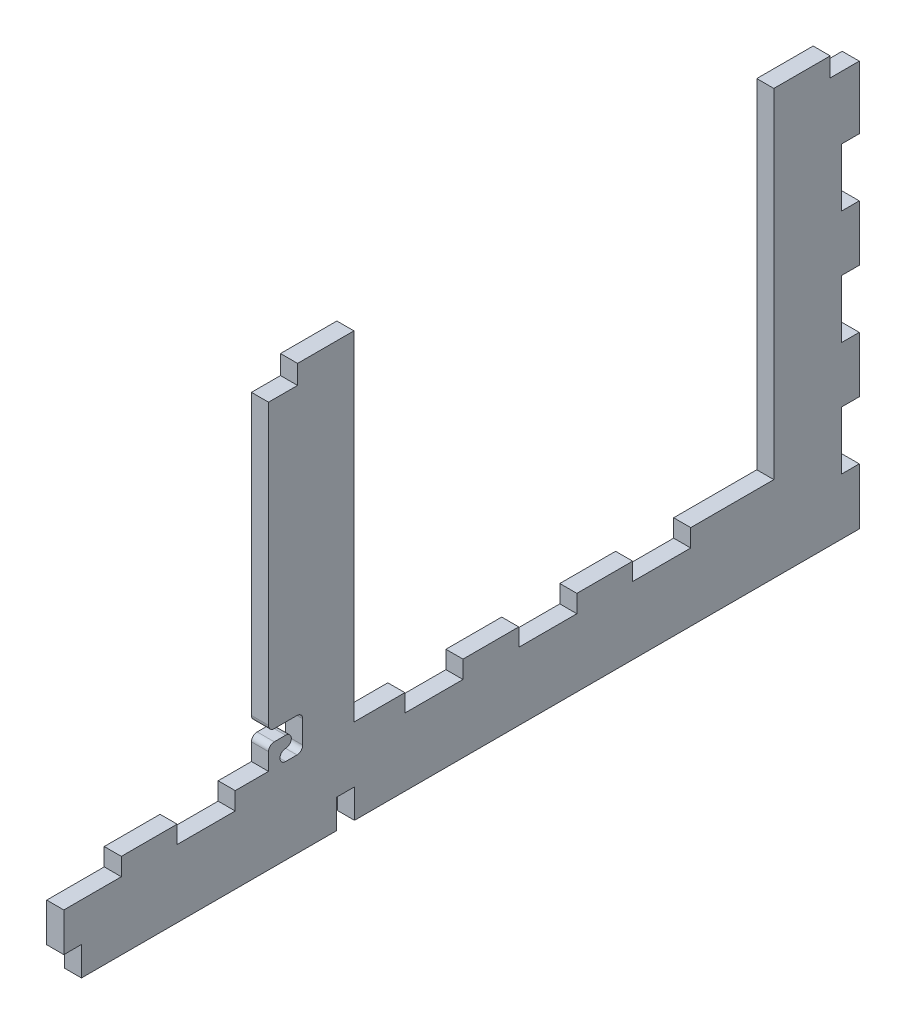
SolidWorks part; units mm, degrees
ref_plane "Front Plane" through (0, 0, 0) normal (0, 0, 1) x (1, 0, 0)
ref_plane "Top Plane" through (0, 0, 0) normal (0, 1, 0) x (1, 0, 0)
ref_plane "Right Plane" through (0, 0, 0) normal (1, 0, 0) x (0, 0, -1)
sketch "Sketch1" plane through (0, 0, 0) normal (0, 1, 0) x (1, 0, 0)
  line L0 (0, 0) -> (0, 103.7444) construction
  line L1 (-36.8722, 0) -> (36.8722, 0) construction
  line L2 (-36.8722, 0) -> (-36.8722, 103.7444)
  line L3 (-36.8722, 103.7444) -> (36.8722, 103.7444)
  line L4 (36.8722, 0) -> (36.8722, 103.7444)
  line L5 (36.8722, 103.7444) -> (36.8722, 0) construction
  line L6 (45.8722, 103.7444) -> (-45.8722, 103.7444) construction
  line L7 (21.0585, 67.686) -> (21.0585, 0)
  line L8 (-21.0585, 67.686) -> (-21.0585, 0)
  line L9 (-36.8722, 0) -> (-21.0585, 0)
  line L10 (21.0585, 0) -> (36.8722, 0)
  line L11 (31.8722, 103.7444) -> (31.8722, 88.7444) construction
  line L12 (34.8722, 103.7444) -> (34.8722, 88.7444) construction
  line L13 (31.8722, 93.7444) -> (34.8722, 93.7444) construction
  line L14 (31.8722, 10) -> (34.8722, 10) construction
  line L15 (31.8722, 88.7444) -> (34.8722, 88.7444) construction
  line L16 (31.8722, 15) -> (34.8722, 15) construction
  line L17 (31.8722, 15) -> (31.8722, 0) construction
  line L18 (34.8722, 15) -> (34.8722, 0) construction
  line L19 (33.3722, 93.7444) -> (33.3722, 88.7444) construction
  line L20 (33.3722, 15) -> (33.3722, 10) construction
  line L21 (34.8722, 100.7444) -> (-34.8722, 100.7444) construction
  line L22 (-34.8722, 100.7444) -> (-34.8722, 103.7444) construction
  line L23 (56.7, -65.95) -> (59.7, -65.95) construction
  arc A0 (21.0585, 67.686) -> (-21.0585, 67.686) centre (0, 67.686) ccw construction
  arc A1 (21.0585, 67.686) -> (-21.0585, 67.686) centre (0, 67.686) ccw
  circle A2 centre (26.5585, 78.4307) radius 1.6 construction
  circle A3 centre (-26.5585, 78.4307) radius 1.6 construction
  circle A4 centre (26.5585, 25.3138) radius 1.6 construction
  circle A5 centre (-26.5585, 25.3138) radius 1.6 construction
  circle A6 centre (26.5585, 78.4307) radius 1.6
  circle A7 centre (-26.5585, 78.4307) radius 1.6
  circle A8 centre (26.5585, 25.3138) radius 1.6
  circle A9 centre (-26.5585, 25.3138) radius 1.6
  dimension "D2" = 2
  dimension "D3" = 10
  dimension "D4" = 5
ref_plane "Plane1" through (34.8722, 0, 0) normal (1, 0, 0) x (0, 0, -1)
sketch "Sketch2" plane through (34.8722, 0, 0) normal (1, 0, 0) x (0, 0, -1)
  line L0 (103.7444, 3) -> (103.7444, -72)
  line L1 (103.7444, -72) -> (-35.95, -72)
  line L2 (0, -57) -> (0, 3)
  line L3 (0, 3) -> (10, 3) construction
  line L4 (10, 3) -> (10, 0) construction
  line L5 (10, 0) -> (15, 0) construction
  line L6 (15, 0) -> (15, -57) construction
  line L7 (15, -57) -> (88.7444, -57)
  line L8 (88.7444, -57) -> (88.7444, 0) construction
  line L9 (88.7444, 0) -> (93.7444, 0) construction
  line L10 (93.7444, 0) -> (93.7444, 3) construction
  line L11 (93.7444, 3) -> (103.7444, 3) construction
  line L12 (103.7444, 0) -> (88.7444, 0) construction
  line L13 (93.7444, 0) -> (103.7444, 0) construction
  line L14 (98.7444, 0) -> (98.7444, 3) construction
  line L15 (-35.95, -72) -> (-65.95, -72) construction
  line L16 (15, 0) -> (0, 0) construction
  line L17 (100.7444, 0) -> (103.7444, 0) construction
  line L18 (103.7444, -46) -> (0, -46) construction
  line L19 (-65.95, -72) -> (-65.95, -57) construction
  line L20 (-65.95, -44.7) -> (-65.95, 65.6444) construction
  line L21 (-35.95, -72) -> (-35.95, -57)
  line L22 (-35.95, -57) -> (-65.95, -57) construction
  line L23 (0, -57) -> (-35.95, -57)
  line L24 (103.7444, 3) -> (88.7444, 3)
  line L25 (88.7444, 3) -> (88.7444, -57)
  line L26 (15, -57) -> (15, 3)
  line L27 (15, 3) -> (0, 3)
  dimension "D1" = 46
  dimension "D2" = 72
  dimension "D3" = 15
  dimension "D4" = 30
extrude "Boss-Extrude1" add sketch "Sketch2" against normal up to vertex (3 mm away) up to point (31.8722, 0, -103.7444)
sketch "Sketch4" plane through (34.8722, 0, 0) normal (1, 0, 0) x (0, 0, -1)
  line L0 (88.7444, 3) -> (88.7444, -57) construction
  line L1 (15, -57) -> (88.7444, -57) construction
  line L2 (15, -57) -> (15, 3) construction
  line L3 (15, 3) -> (0, 3) construction
  line L4 (0, -57) -> (0, 3) construction
  line L5 (0, -57) -> (-35.95, -57) construction
  line L6 (-35.95, -72) -> (-35.95, -57) construction
  line L7 (103.7444, -72) -> (-35.95, -72) construction
  line L8 (103.7444, 3) -> (103.7444, -72) construction
  line L9 (103.7444, 3) -> (88.7444, 3) construction
  line L10 (88.7444, 3) -> (88.7444, -57) construction
  line L11 (15, -57) -> (88.7444, -57) construction
  line L12 (15, -57) -> (15, 3) construction
  line L13 (15, 3) -> (0, 3) construction
  line L14 (0, -57) -> (0, 3) construction
  line L15 (0, -57) -> (-35.95, -57) construction
  line L16 (-35.95, -72) -> (-35.95, -57) construction
  line L17 (103.7444, -72) -> (-35.95, -72) construction
  line L18 (103.7444, 3) -> (103.7444, -72) construction
  line L19 (103.7444, 3) -> (88.7444, 3) construction
  line L20 (100.7444, 0) -> (100.7444, -72) construction
  line L21 (100.7444, 0) -> (88.7444, 0) construction
  line L22 (100.7444, 0) -> (103.7444, 0) construction
  line L23 (100.7444, 0) -> (100.7444, 3) construction
  line L25 (88.7444, -57) -> (103.7444, -57) construction
  line L26 (98.7444, -0.75) -> (103.7444, -0.75)
  line L27 (103.7444, 3) -> (98.7444, 3)
  line L28 (98.7444, 3) -> (98.7444, -0.75)
  line L29 (103.7444, -0.75) -> (103.7444, 3)
  line L30 (103.7444, -12) -> (100.7444, -12)
  line L31 (103.7444, -52) -> (103.7444, -62)
  line L32 (103.7444, -22) -> (100.7444, -22)
  line L33 (100.7444, -62) -> (100.7444, -52)
  line L34 (103.7444, -32) -> (100.7444, -32)
  line L35 (100.7444, -42) -> (100.7444, -32)
  line L36 (103.7444, -42) -> (100.7444, -42)
  line L37 (103.7444, -32) -> (103.7444, -42)
  line L38 (103.7444, -52) -> (100.7444, -52)
  line L39 (100.7444, -12) -> (100.7444, -22)
  line L40 (103.7444, -62) -> (100.7444, -62)
  line L41 (103.7444, -22) -> (103.7444, -12)
  line L42 (-32.95, -60) -> (-32.95, -72) construction
  line L43 (15, -57) -> (15, -72) construction
  line L44 (12, -57) -> (12, -72) construction
  line L45 (15, -57) -> (12, -57) construction
  line L46 (103.7444, -60) -> (-32.95, -60) construction
  line L48 (0, 3) -> (5, 3)
  line L49 (0, 3) -> (0, -0.75)
  line L50 (0, -0.75) -> (5, -0.75)
  line L51 (5, 3) -> (5, -0.75)
  line L53 (-32.95, -60) -> (-35.95, -60) construction
  line L54 (-32.95, -60) -> (-32.95, -57) construction
  line L55 (-25.95, -58.5) -> (-35.95, -58.5) construction
  line L56 (15, -67) -> (12, -67)
  line L57 (15, -67) -> (15, -72)
  line L58 (15, -72) -> (12, -72)
  line L59 (12, -67) -> (12, -72)
  line L60 (-32.95, -67) -> (-35.95, -67)
  line L61 (-32.95, -67) -> (-32.95, -72)
  line L62 (-32.95, -72) -> (-35.95, -72)
  line L63 (-35.95, -67) -> (-35.95, -72)
  line L64 (-5.95, -57) -> (-15.95, -57)
  line L65 (-25.95, -57) -> (-25.95, -60)
  line L66 (-5.95, -60) -> (-15.95, -60)
  line L67 (-15.95, -57) -> (-15.95, -60)
  line L68 (-25.95, -58.5) -> (-15.95, -58.5) construction
  line L69 (4.05, -58.5) -> (-5.95, -58.5) construction
  line L70 (-25.95, -60) -> (-35.95, -60)
  line L71 (-5.95, -57) -> (-5.95, -60)
  line L72 (-35.95, -60) -> (-35.95, -57)
  line L73 (34.05, -58.5) -> (44.05, -58.5) construction
  line L74 (-5.95, -58.5) -> (-15.95, -58.5) construction
  line L75 (-35.95, -57) -> (-25.95, -57)
  line L76 (4.05, -58.5) -> (14.05, -58.5) construction
  line L77 (14.05, -58.5) -> (24.05, -58.5) construction
  line L78 (24.05, -58.5) -> (34.05, -58.5) construction
  line L79 (24.05, -60) -> (34.05, -60)
  line L80 (24.05, -60) -> (24.05, -57)
  line L81 (24.05, -57) -> (34.05, -57)
  line L82 (34.05, -60) -> (34.05, -57)
  line L83 (44.05, -57) -> (54.05, -57)
  line L84 (44.05, -57) -> (44.05, -60)
  line L85 (44.05, -60) -> (54.05, -60)
  line L86 (54.05, -57) -> (54.05, -60)
  line L87 (64.05, -57) -> (74.05, -57)
  line L88 (64.05, -57) -> (64.05, -60)
  line L89 (64.05, -60) -> (74.05, -60)
  line L90 (74.05, -57) -> (74.05, -60)
  line L91 (44.05, -58.5) -> (54.05, -58.5) construction
  line L92 (54.05, -58.5) -> (64.05, -58.5) construction
  line L93 (64.05, -58.5) -> (74.05, -58.5) construction
  dimension "D1" = 10
  dimension "D2" = 10
  dimension "D3" = 5
  dimension "D4" = 10
sketch "Sketch5" plane through (34.8722, 0, 0) normal (1, 0, 0) x (0, 0, -1)
  line L0 (103.8444, -31.9) -> (100.6444, -31.9)
  line L1 (100.6444, -31.9) -> (100.6444, -42.1)
  line L2 (100.6444, -42.1) -> (103.8444, -42.1)
  line L3 (103.8444, -42.1) -> (103.8444, -31.9)
  line L4 (103.7444, -32) -> (100.7444, -32)
  line L5 (100.7444, -32) -> (100.7444, -42)
  line L6 (100.7444, -42) -> (103.7444, -42)
  line L7 (103.7444, -42) -> (103.7444, -32)
  line L8 (103.7444, -32) -> (100.7444, -32) construction
  line L9 (100.7444, -32) -> (100.7444, -42) construction
  line L10 (100.7444, -42) -> (103.7444, -42) construction
  line L11 (103.7444, -42) -> (103.7444, -32) construction
  line L12 (103.7444, -62) -> (103.7444, -52)
  line L13 (100.7444, -62) -> (103.7444, -62)
  line L14 (100.7444, -52) -> (100.7444, -62)
  line L15 (103.7444, -52) -> (100.7444, -52)
  line L16 (103.7444, -62) -> (103.7444, -52) construction
  line L17 (100.7444, -62) -> (103.7444, -62) construction
  line L18 (100.7444, -52) -> (100.7444, -62) construction
  line L19 (103.7444, -52) -> (100.7444, -52) construction
  line L20 (103.7444, -12) -> (100.7444, -12)
  line L21 (100.7444, -12) -> (100.7444, -22)
  line L22 (100.7444, -22) -> (103.7444, -22)
  line L23 (103.7444, -22) -> (103.7444, -12)
  line L24 (103.7444, -12) -> (100.7444, -12) construction
  line L25 (100.7444, -12) -> (100.7444, -22) construction
  line L26 (100.7444, -22) -> (103.7444, -22) construction
  line L27 (103.7444, -22) -> (103.7444, -12) construction
  line L28 (5, 3) -> (0, 3)
  line L29 (0, 3) -> (0, -0.75)
  line L30 (0, -0.75) -> (5, -0.75)
  line L31 (5, -0.75) -> (5, 3)
  line L32 (5, 3) -> (0, 3) construction
  line L33 (0, 3) -> (0, -0.75) construction
  line L34 (0, -0.75) -> (5, -0.75) construction
  line L35 (5, -0.75) -> (5, 3) construction
  line L36 (98.7444, -0.75) -> (103.7444, -0.75)
  line L37 (103.7444, -0.75) -> (103.7444, 3)
  line L38 (103.7444, 3) -> (98.7444, 3)
  line L39 (98.7444, 3) -> (98.7444, -0.75)
  line L40 (98.7444, -0.75) -> (103.7444, -0.75) construction
  line L41 (103.7444, -0.75) -> (103.7444, 3) construction
  line L42 (103.7444, 3) -> (98.7444, 3) construction
  line L43 (98.7444, 3) -> (98.7444, -0.75) construction
  line L44 (-25.95, -60) -> (-25.95, -57)
  line L45 (-35.95, -60) -> (-25.95, -60)
  line L46 (-35.95, -57) -> (-35.95, -60)
  line L47 (-25.95, -57) -> (-35.95, -57)
  line L48 (-25.95, -60) -> (-25.95, -57) construction
  line L49 (-35.95, -60) -> (-25.95, -60) construction
  line L50 (-35.95, -57) -> (-35.95, -60) construction
  line L51 (-25.95, -57) -> (-35.95, -57) construction
  line L52 (-32.95, -67) -> (-35.95, -67)
  line L53 (-35.95, -67) -> (-35.95, -72)
  line L54 (-35.95, -72) -> (-32.95, -72)
  line L55 (-32.95, -72) -> (-32.95, -67)
  line L56 (-32.95, -67) -> (-35.95, -67) construction
  line L57 (-35.95, -67) -> (-35.95, -72) construction
  line L58 (-35.95, -72) -> (-32.95, -72) construction
  line L59 (-32.95, -72) -> (-32.95, -67) construction
  line L60 (15, -67) -> (12, -67)
  line L61 (15, -72) -> (15, -67)
  line L62 (12, -72) -> (15, -72)
  line L63 (12, -67) -> (12, -72)
  line L64 (15, -67) -> (12, -67) construction
  line L65 (15, -72) -> (15, -67) construction
  line L66 (12, -72) -> (15, -72) construction
  line L67 (12, -67) -> (12, -72) construction
  line L68 (54.05, -57) -> (44.05, -57)
  line L69 (54.05, -60) -> (54.05, -57)
  line L70 (44.05, -60) -> (54.05, -60)
  line L71 (44.05, -57) -> (44.05, -60)
  line L72 (54.05, -57) -> (44.05, -57) construction
  line L73 (54.05, -60) -> (54.05, -57) construction
  line L74 (44.05, -60) -> (54.05, -60) construction
  line L75 (44.05, -57) -> (44.05, -60) construction
  line L76 (24.05, -60) -> (34.05, -60)
  line L77 (34.05, -60) -> (34.05, -57)
  line L78 (34.05, -57) -> (24.05, -57)
  line L79 (24.05, -57) -> (24.05, -60)
  line L80 (24.05, -60) -> (34.05, -60) construction
  line L81 (34.05, -60) -> (34.05, -57) construction
  line L82 (34.05, -57) -> (24.05, -57) construction
  line L83 (24.05, -57) -> (24.05, -60) construction
  line L84 (-15.95, -60) -> (-5.95, -60)
  line L85 (-15.95, -57) -> (-15.95, -60)
  line L86 (-5.95, -57) -> (-15.95, -57)
  line L87 (-5.95, -60) -> (-5.95, -57)
  line L88 (-15.95, -60) -> (-5.95, -60) construction
  line L89 (-15.95, -57) -> (-15.95, -60) construction
  line L90 (-5.95, -57) -> (-15.95, -57) construction
  line L91 (-5.95, -60) -> (-5.95, -57) construction
  line L92 (74.05, -57) -> (64.05, -57)
  line L93 (64.05, -57) -> (64.05, -60)
  line L94 (64.05, -60) -> (74.05, -60)
  line L95 (74.05, -60) -> (74.05, -57)
  line L96 (74.05, -57) -> (64.05, -57) construction
  line L97 (64.05, -57) -> (64.05, -60) construction
  line L98 (64.05, -60) -> (74.05, -60) construction
  line L99 (74.05, -60) -> (74.05, -57) construction
  line L100 (103.8444, -62.1) -> (103.8444, -51.9)
  line L101 (103.8444, -51.9) -> (100.6444, -51.9)
  line L102 (100.6444, -51.9) -> (100.6444, -62.1)
  line L103 (100.6444, -62.1) -> (103.8444, -62.1)
  line L104 (103.8444, -11.9) -> (100.6444, -11.9)
  line L105 (100.6444, -11.9) -> (100.6444, -22.1)
  line L106 (100.6444, -22.1) -> (103.8444, -22.1)
  line L107 (103.8444, -22.1) -> (103.8444, -11.9)
  line L108 (5.1, 3.1) -> (-0.1, 3.1) construction
  line L109 (-0.1, 3.1) -> (-0.1, -0.85)
  line L110 (-0.1, -0.85) -> (5.1, -0.85)
  line L111 (5.1, -0.85) -> (5.1, 3.1) construction
  line L112 (98.6444, -0.85) -> (103.8444, -0.85)
  line L113 (103.8444, -0.85) -> (103.8444, 3.1)
  line L114 (103.8444, 3.1) -> (98.6444, 3.1) construction
  line L115 (98.6444, 3.1) -> (98.6444, -0.85) construction
  line L116 (-25.85, -60.1) -> (-25.85, -56.9)
  line L117 (-25.85, -56.9) -> (-36.05, -56.9)
  line L118 (-36.05, -56.9) -> (-36.05, -60.1)
  line L119 (-36.05, -60.1) -> (-25.85, -60.1)
  line L120 (-32.85, -66.9) -> (-36.05, -66.9)
  line L121 (-36.05, -66.9) -> (-36.05, -72.1)
  line L122 (-36.05, -72.1) -> (-32.85, -72.1)
  line L123 (-32.85, -72.1) -> (-32.85, -66.9)
  line L124 (15.1, -66.9) -> (11.9, -66.9)
  line L125 (11.9, -66.9) -> (11.9, -72.1)
  line L126 (11.9, -72.1) -> (15.1, -72.1)
  line L127 (15.1, -72.1) -> (15.1, -66.9)
  line L128 (54.15, -56.9) -> (43.95, -56.9)
  line L129 (43.95, -56.9) -> (43.95, -60.1)
  line L130 (43.95, -60.1) -> (54.15, -60.1)
  line L131 (54.15, -60.1) -> (54.15, -56.9)
  line L132 (23.95, -60.1) -> (34.15, -60.1)
  line L133 (34.15, -60.1) -> (34.15, -56.9)
  line L134 (34.15, -56.9) -> (23.95, -56.9)
  line L135 (23.95, -56.9) -> (23.95, -60.1)
  line L136 (-16.05, -60.1) -> (-5.85, -60.1)
  line L137 (-5.85, -60.1) -> (-5.85, -56.9)
  line L138 (-5.85, -56.9) -> (-16.05, -56.9)
  line L139 (-16.05, -56.9) -> (-16.05, -60.1)
  line L140 (74.15, -56.9) -> (63.95, -56.9)
  line L141 (63.95, -56.9) -> (63.95, -60.1)
  line L142 (63.95, -60.1) -> (74.15, -60.1)
  line L143 (74.15, -60.1) -> (74.15, -56.9)
  line L144 (103.8444, 2.5) -> (88.7444, 2.5) construction
  line L145 (88.7444, 3) -> (88.7444, -57) construction
  line L146 (103.7444, 3) -> (88.7444, 3) construction
  line L147 (98.6444, -0.85) -> (98.6444, 2.5)
  line L148 (98.6444, 2.5) -> (88.7444, 2.5)
  line L149 (88.7444, 2.5) -> (88.7444, 3.1)
  line L150 (88.7444, 3.1) -> (103.8444, 3.1)
  line L151 (5.1, -0.85) -> (5.1, 2.5)
  line L152 (5.1, 2.5) -> (15, 2.5)
  line L153 (15, 2.5) -> (15, 3.1)
  line L154 (15, 3.1) -> (-0.1, 3.1)
  line L155 (15, -57) -> (15, 3) construction
  dimension "D14" = 0.5
  dimension "D1" = 0
  dimension "D2" = 0
  dimension "D3" = 0
  dimension "D4" = 0
  dimension "D5" = 0
  dimension "D6" = 0
  dimension "D7" = 0
  dimension "D8" = 0
  dimension "D9" = 0
  dimension "D10" = 0
  dimension "D11" = 0
  dimension "D12" = 0
  dimension "D13" = 0.1
extrude "Cut-Extrude1" cut sketch "Sketch5" against normal through all
sketch "Sketch6" plane through (34.8722, 0, 0) normal (1, 0, 0) x (0, 0, -1)
  line L0 (6, -57) -> (2, -57) construction
  line L1 (2, -57) -> (2, -55) construction
  line L2 (2, -55) -> (4, -55) construction
  line L3 (0, -57) -> (15, -57) construction
  line L4 (0, -57) -> (0, 3) construction
  line L5 (0, -57) -> (0, 3) construction
  line L6 (4, -55) -> (4, -53) construction
  line L7 (4, -53) -> (0, -53) construction
  line L8 (0, -53) -> (0, -51) construction
  line L9 (0, -51) -> (6, -51) construction
  line L10 (6, -51) -> (6, -57) construction
  line L11 (4, -55) -> (6, -55) construction
  line L12 (4, -55) -> (4, -57) construction
  line L13 (4, -53) -> (4, -51) construction
  line L14 (0, -50) -> (0, -54)
  line L15 (1, -53) -> (3, -53)
  line L16 (5, -51) -> (1, -51)
  line L17 (6, -52) -> (6, -56)
  line L18 (5, -57) -> (3, -57)
  line L19 (2, -56) -> (0, -56) construction
  arc A0 (0, -50) -> (1, -51) centre (1, -50) ccw
  arc A1 (1, -53) -> (0, -54) centre (1, -54) ccw
  arc A2 (5, -51) -> (6, -52) centre (5, -52) cw
  arc A3 (3, -53) -> (3, -55) centre (3, -54) cw
  arc A5 (3, -55) -> (3, -57) centre (3, -56) ccw
  arc A7 (6, -56) -> (5, -57) centre (5, -56) cw
  dimension "D1" = 2
extrude "Cut-Extrude2" cut sketch "Sketch6" against normal through all
